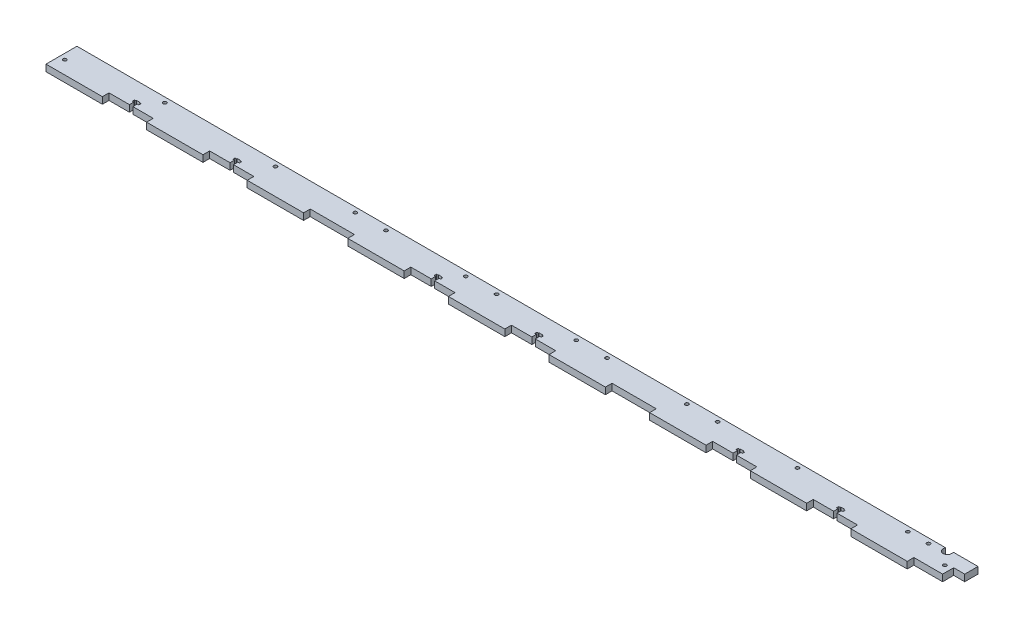
SolidWorks part; units mm, degrees
ref_plane "Płaszczyzna przednia" through (0, 0, 0) normal (0, 0, 1) x (1, 0, 0)
ref_plane "Płaszczyzna górna" through (0, 0, 0) normal (0, 1, 0) x (1, 0, 0)
ref_plane "Płaszczyzna prawa" through (0, 0, 0) normal (1, 0, 0) x (0, 0, -1)
sketch "Szkic1" plane through (0, -418.8763, -418.8763) normal (0, 1, 0) x (1, 0, 0)
  line L1 (-1145.3685, -408.8763) -> (-265.3685, -408.8763)
  line L2 (-1145.3685, -477.8763) -> (-1145.3685, -408.8763)
  line L3 (-265.3685, -408.8763) -> (-265.3685, -477.8763)
  line L4 (-1145.3685, -477.8763) -> (-265.3685, -477.8763)
  line L5 (-335.8685, -421.8763) -> (-1070.8685, -421.8763)
  line L6 (-335.8685, -421.8763) -> (-335.8685, -449.8763)
  line L7 (-335.8685, -449.8763) -> (-1070.8685, -449.8763)
  line L8 (-1070.8685, -421.8763) -> (-1070.8685, -449.8763)
  line L10 (-482.1641, -408.8763) -> (-356.3685, -408.8763) construction
  line L11 (-265.3685, -1108.8763) -> (-265.3685, -528.8763) construction
  dimension "D1" = 0
  dimension "D2" = 0
  dimension "D3" = 69
  dimension "D4" = 880
  dimension "D5" = 28
  dimension "D6" = 28
  dimension "D7" = 70.5
  dimension "D8" = 74.5
extrude "Dodanie-wyciągnięcie2" add sketch "Szkic1" along normal blind 3 and the other way blind 3
sketch "Szkic2" plane through (0, 0, 59) normal (0, 0, 1) x (1, 0, 0)
  line L0 (-1145.3685, -415.8763) -> (-265.3685, -415.8763) construction
  line L1 (-1145.3685, -421.8763) -> (-1105.3685, -421.8763)
  line L2 (-1145.3685, -421.8763) -> (-1145.3685, -415.8763)
  line L3 (-1145.3685, -415.8763) -> (-1105.3685, -415.8763)
  line L4 (-1105.3685, -421.8763) -> (-1105.3685, -415.8763)
  dimension "D1" = 40
extrude "Wytnij-wyciągnięcie1" cut sketch "Szkic2" against normal blind 6
pattern_linear "Szyk liniowy1" count 13 spacing 91 along (1, 0, 0) of "Wytnij-wyciągnięcie1"
sketch "Szkic3" plane through (0, -415.8763, 0) normal (0, 1, 0) x (1, 0, 0)
  line L0 (-1105.3685, -53) -> (-1145.3685, -53) construction
  line L1 (-1032.8185, -53) -> (-1035.9185, -53)
  line L2 (-1032.8185, -53) -> (-1032.8185, -49)
  line L3 (-1032.8185, -46.5) -> (-1035.9185, -46.5)
  line L4 (-1035.9185, -53) -> (-1035.9185, -49)
  line L5 (-1032.8185, -47) -> (-1032.8185, -46.5)
  line L6 (-1031.4435, -47) -> (-1032.8185, -47)
  line L7 (-1031.4435, -47) -> (-1031.4435, -49)
  line L8 (-1031.4435, -49) -> (-1032.8185, -49)
  line L9 (-1037.2935, -47) -> (-1037.2935, -49)
  line L10 (-1035.9185, -47) -> (-1037.2935, -47)
  line L11 (-1035.9185, -47) -> (-1035.9185, -46.5)
  line L12 (-1035.9185, -49) -> (-1037.2935, -49)
  line L14 (-1054.3685, -53) -> (-1054.3685, -59) construction
  point P14 (-1034.3685, -53)
  dimension "D1" = 6.5
  dimension "D2" = 3.1
  dimension "D3" = 5.85
  dimension "D4" = 1.375
  dimension "D5" = 0.5
  dimension "D6" = 2
  dimension "D7" = 20
extrude "Wytnij-wyciągnięcie2" cut sketch "Szkic3" against normal blind 6
ref_plane "Płaszczyzna1" through (-705.3685, 0, 0) normal (-1, 0, 0) x (0, 0, 1)
sketch "Szkic9" plane through (0, -415.8763, 0) normal (0, 1, 0) x (1, 0, 0)
  circle A2 centre (-300.7063, -17.43) radius 12.5 construction
  circle A3 centre (-300.7063, -17.43) radius 12.5
extrude "Wytnij-wyciągnięcie6" cut sketch "Szkic9" against normal blind 6
sketch "Szkic10" plane through (0, -421.8763, 0) normal (0, -1, 0) x (1, 0, 0)
  circle A0 centre (-316.2063, 32.93) radius 1.5 construction
  circle A1 centre (-316.2063, 32.93) radius 1.5
  circle A10 centre (-316.2063, 32.93) radius 3.75
  dimension "D3" = 7.5
sketch "Szkic11" plane through (0, -421.8763, 0) normal (0, -1, 0) x (1, 0, 0)
  line L0 (-319.9563, 32.93) -> (-319.9563, 30.9761)
  line L1 (-319.9563, 30.9761) -> (-312.4563, 30.9761)
  line L2 (-312.4563, 30.9761) -> (-312.4563, 32.93)
  circle A4 centre (-316.2063, 32.93) radius 3.75 construction
  arc A6 (-312.4563, 32.93) -> (-319.9563, 32.93) centre (-316.2063, 32.93) ccw
extrude "Wytnij-wyciągnięcie7" cut sketch "Szkic11" against normal blind 6
sketch "Szkic13" plane through (0, -415.8763, 0) normal (0, 1, 0) x (1, 0, 0)
  line L0 (-265.3685, -44) -> (-265.3685, -59)
  line L1 (-265.3685, -44) -> (-290.3685, -44)
  line L2 (-265.3685, -59) -> (-290.3685, -59)
  line L3 (-290.3685, -44) -> (-290.3685, -59)
  line L5 (-265.3685, -59) -> (-265.3685, 10) construction
  line L6 (-286.3685, -59) -> (-265.3685, -59) construction
  dimension "D1" = 0
  dimension "D2" = 25
  dimension "D3" = 0
extrude "Wytnij-wyciągnięcie8" cut sketch "Szkic13" against normal blind 6
pattern_linear "Szyk liniowy3" count 2 spacing 91 along (1, 0, 0) count 3 spacing 273 along (1, 0, 0) of "Wytnij-wyciągnięcie2"
sketch "Szkic14" plane through (0, -415.8763, 0) normal (0, 1, 0) x (1, 0, 0)
  line L0 (-1105.3685, -59) -> (-1105.3685, -31)
  line L1 (-1105.3685, -59) -> (-290.3685, -59)
  line L2 (-1105.3685, -31) -> (-290.3685, -31)
  line L3 (-290.3685, -59) -> (-290.3685, -31)
  line L4 (-290.3685, -44) -> (-290.3685, -53) construction
  line L5 (-1070.8685, -31) -> (-335.8685, -31) construction
  point P0 (-290.3685, -48.5)
  dimension "D1" = 0
  dimension "D2" = 0
extrude "Wytnij-wyciągnięcie9" cut sketch "Szkic14" against normal blind 10 flip side to cut
sketch "Szkic15" plane through (0, -415.8763, 0) normal (0, 1, 0) x (1, 0, 0)
  circle A0 centre (-1100.3685, -47) radius 1.55 construction
  circle A3 centre (-306.3662, -45) radius 1.55 construction
  circle A4 centre (-1100.3685, -47) radius 1.55
  circle A7 centre (-306.3662, -45) radius 1.55
extrude "Wytnij-wyciągnięcie10" cut sketch "Szkic15" against normal blind 10
sketch "Szkic16" plane through (0, -415.8763, 0) normal (0, 1, 0) x (1, 0, 0)
  line L1 (-350.4185, -42.8) -> (-347.3185, -42.8)
  line L6 (-361.9133, -34.7) -> (-361.9133, -36.3)
  line L7 (-361.9133, -36.3) -> (-359.0133, -36.3)
  line L8 (-359.0133, -36.3) -> (-359.0133, -34.7)
  line L9 (-359.0133, -34.7) -> (-361.9133, -34.7)
  line L10 (-361.9133, -34.7) -> (-361.9133, -36.3)
  line L11 (-361.9133, -36.3) -> (-359.0133, -36.3)
  line L12 (-359.0133, -36.3) -> (-359.0133, -34.7)
  line L13 (-359.0133, -34.7) -> (-361.9133, -34.7)
  ellipse E3 centre (-1042.5985, -42.8716) end of major axis (-1044.1485, -42.8716) minor radius 0.2692
  ellipse E4 centre (-942.5985, -42.8716) end of major axis (-944.1485, -42.8716) minor radius 0.2692
  ellipse E5 centre (-881.7185, -42.8716) end of major axis (-880.1685, -42.8716) minor radius 0.2692
  point P37 (-361.9133, -35.5)
  point P40 (-348.8685, -42.8)
  dimension "D1" = 0
sketch "Szkic18" plane through (0, -415.8763, 0) normal (0, 1, 0) x (1, 0, 0)
  line L0 (-1105.3685, -31) -> (-319.9563, -31) construction
  circle A0 centre (-330.6385, -35.5) radius 1.55
  dimension "D1" = 3.1
  dimension "D2" = 18.23
  dimension "D4" = 4.5
extrude "Wytnij-wyciągnięcie11" cut sketch "Szkic18" against normal blind 10
sketch "Szkic19" plane through (0, -415.8763, 0) normal (0, 1, 0) x (1, 0, 0)
  line L0 (-1105.3685, -31) -> (-319.9563, -31) construction
  circle A0 centre (-1021.3685, -35.5) radius 1.55
  circle A1 centre (-849.2185, -35.5) radius 1.55
  dimension "D1" = 3.1
  dimension "D2" = 3.1
  dimension "D3" = 21.23
  dimension "D4" = 32.5
  dimension "D5" = 4.5
  dimension "D7" = 4.5
extrude "Wytnij-wyciągnięcie12" cut sketch "Szkic19" against normal blind 10
pattern_linear "Szyk liniowy4" count 6 spacing 100 along (1, 0, 0) of "Wytnij-wyciągnięcie12"
sketch "Szkic20" plane through (0, -415.8763, 0) normal (0, 1, 0) x (1, 0, 0)
  line L0 (-290.3685, -53) -> (-290.3685, -43)
  line L1 (-290.3685, -53) -> (-300.3685, -53)
  line L2 (-290.3685, -43) -> (-300.3685, -43)
  line L3 (-300.3685, -53) -> (-300.3685, -43)
  line L4 (-290.3685, -31) -> (-290.3685, -53) construction
  line L5 (-300.3685, -43) -> (-300.3685, -59) construction
  line L6 (-265.3685, -43) -> (-300.3685, -43) construction
  dimension "D1" = 0
  dimension "D2" = 0
extrude "Wytnij-wyciągnięcie13" cut sketch "Szkic20" against normal blind 10
equation "\"tolerancja_wpusy\"=0.2"
equation "\"dlugosc_wpustu_duzy\"=20"
equation "\"srednica_otworu_M3\"=3.1"
equation "\"szerokosc_nogi_T\"=3.1"
equation "\"dlugosc_T_30\"=11"
equation "\"grubosc_na_nakretke_kwadrat\"=2"
equation "\"szerokosc_na_nakretke_kwadrat\"=5.85"
equation "\"wyokosc_nadstawki_T\"=0.5"
equation "\"dlugosc_T_20_6\"=14"
equation "\"D2@Szkic3\"=\"szerokosc_nogi_T\""
equation "\"D3@Szkic3\"=\"szerokosc_na_nakretke_kwadrat\""
equation "\"D4@Szkic3\"=(\"szerokosc_na_nakretke_kwadrat\"-\"szerokosc_nogi_T\")/2"
equation "\"D5@Szkic3\"=\"wyokosc_nadstawki_T\""
equation "\"D6@Szkic3\"=\"grubosc_na_nakretke_kwadrat\""
equation "\"D1@Szkic18\"=\"srednica_otworu_M3\""
equation "\"D1@Szkic19\" = \"srednica_otworu_M3\""
equation "\"D2@Szkic19\"=\"srednica_otworu_M3\""
